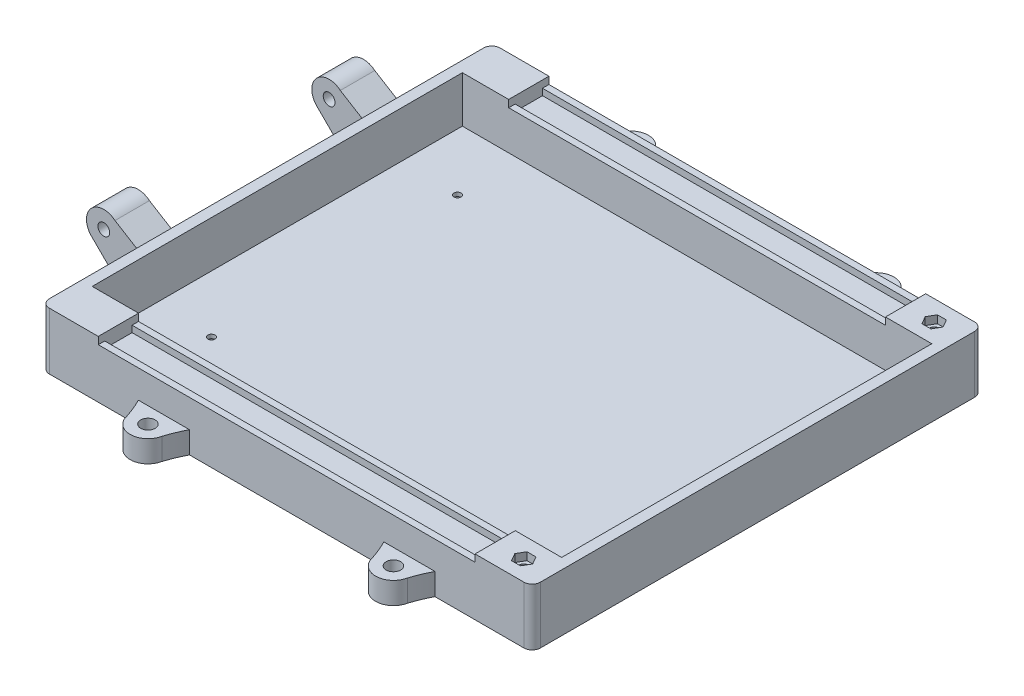
SolidWorks part; units mm, degrees
note: '?' marks a value the reader was unsure of.
ref_plane "Front Plane" through (0, 0, 0) normal (0, 0, 1) x (1, 0, 0)
ref_plane "Top Plane" through (0, 0, 0) normal (0, 1, 0) x (1, 0, 0)
ref_plane "Right Plane" through (0, 0, 0) normal (1, 0, 0) x (0, 0, -1)
sketch "Sketch18" plane through (0, 0, 0) normal (0, 1, 0) x (1, 0, 0)
  line L1 (-114.02, -85.96) -> (114.02, -85.96)
  line L2 (-114.02, -85.96) -> (-114.02, 85.96)
  line L3 (-114.02, 85.96) -> (114.02, 85.96)
  line L4 (114.02, -85.96) -> (114.02, 85.96)
  line L5 (-114.02, -85.96) -> (114.02, 85.96) construction
  line L6 (-114.02, 85.96) -> (114.02, -85.96) construction
  point P0 (0, 0)
  dimension "D1" = 171.92
  dimension "D2" = 228.04
extrude "Boss-Extrude6" add sketch "Sketch18" along normal blind 26.5
sketch "Sketch20" plane through (0, 26.5, 0) normal (0, 1, 0) x (1, 0, 0)
  line L0 (114.02, 85.96) -> (-114.02, 85.96) construction
  line L1 (109.02, -85.96) -> (-109.02, -85.96)
  line L2 (109.02, -85.96) -> (109.02, 85.96)
  line L3 (109.02, 85.96) -> (-109.02, 85.96)
  line L4 (-109.02, -85.96) -> (-109.02, 85.96)
  line L5 (109.02, -85.96) -> (-109.02, 85.96) construction
  line L6 (109.02, 85.96) -> (-109.02, -85.96) construction
  point P0 (0, 0)
  dimension "D1" = 218.04
extrude "Cut-Extrude6" cut sketch "Sketch20" against normal blind 21.5
sketch "Sketch22" plane through (0, 0, 0) normal (0, 1, 0) x (1, 0, 0)
  line L1 (-114.02, -85.96) -> (114.02, -85.96)
  line L2 (-114.02, -85.96) -> (-114.02, -104.66)
  line L3 (-114.02, -104.66) -> (114.02, -104.66)
  line L4 (114.02, -85.96) -> (114.02, -104.66)
  dimension "D1" = 18.7
extrude "Boss-Extrude7" add sketch "Sketch22" along normal blind 26.5
sketch "Sketch23" plane through (0, 0, 0) normal (0, 1, 0) x (1, 0, 0)
  line L1 (114.02, 85.96) -> (-114.02, 85.96)
  line L2 (114.02, 85.96) -> (114.02, 104.66)
  line L3 (114.02, 104.66) -> (-114.02, 104.66)
  line L4 (-114.02, 85.96) -> (-114.02, 104.66)
  dimension "D1" = 18.7
extrude "Boss-Extrude8" add sketch "Sketch23" along normal blind 26.5
sketch "Sketch24" plane through (0, 26.5, 0) normal (0, 1, 0) x (1, 0, 0)
  line L1 (-87.5, 104.66) -> (87.5, 104.66)
  line L2 (-87.5, 104.66) -> (-87.5, 85.96)
  line L3 (-87.5, 85.96) -> (87.5, 85.96)
  line L4 (87.5, 104.66) -> (87.5, 85.96)
  dimension "D1" = 18.7
  dimension "D2" = 175
extrude "Cut-Extrude7" cut sketch "Sketch24" against normal blind 3.35
sketch "Sketch25" plane through (0, 26.5, 0) normal (0, 1, 0) x (1, 0, 0)
  line L1 (-87.5, -85.96) -> (87.5, -85.96)
  line L2 (-87.5, -85.96) -> (-87.5, -104.66)
  line L3 (-87.5, -104.66) -> (87.5, -104.66)
  line L4 (87.5, -85.96) -> (87.5, -104.66)
  dimension "D1" = 175
  dimension "D2" = 18.7
extrude "Cut-Extrude8" cut sketch "Sketch25" against normal blind 3.35
ref_point "Point2"
ref_point "Point3"
sketch "Sketch27" plane through (0, 23.15, 0) normal (0, 1, 0) x (1, 0, 0)
  line L0 (-87.5, -85.96) -> (-87.5, -104.66) construction
  line L1 (87.5, -88.96) -> (-87.5, -88.96)
  line L2 (87.5, -88.96) -> (87.5, -101.66)
  line L3 (87.5, -101.66) -> (-87.5, -101.66)
  line L4 (-87.5, -88.96) -> (-87.5, -101.66)
  line L5 (87.5, -88.96) -> (-87.5, -101.66) construction
  line L6 (87.5, -101.66) -> (-87.5, -88.96) construction
  point P0 (0, -95.31)
  dimension "D1" = 12.7
extrude "Cut-Extrude9" cut sketch "Sketch27" against normal blind 3
sketch "Sketch28" plane through (0, 23.15, 0) normal (0, 1, 0) x (1, 0, 0)
  line L0 (-87.5, 104.66) -> (-87.5, 85.96) construction
  line L1 (87.5, 88.96) -> (-87.5, 88.96)
  line L2 (87.5, 88.96) -> (87.5, 101.66)
  line L3 (87.5, 101.66) -> (-87.5, 101.66)
  line L4 (-87.5, 88.96) -> (-87.5, 101.66)
  line L5 (87.5, 88.96) -> (-87.5, 101.66) construction
  line L6 (87.5, 101.66) -> (-87.5, 88.96) construction
  point P0 (0, 95.31)
  dimension "D1" = 12.7
extrude "Cut-Extrude10" cut sketch "Sketch28" against normal blind 3
sketch "Sketch29" plane through (0, 5, 0) normal (0, 1, 0) x (1, 0, 0)
  line L0 (-109.02, 85.96) -> (-109.02, -85.96) construction
  line L1 (106.02, -60.96) -> (-87.02, -60.96)
  line L2 (106.02, -60.96) -> (106.02, 60.96)
  line L3 (106.02, 60.96) -> (-87.02, 60.96)
  line L4 (-87.02, -60.96) -> (-87.02, 60.96)
  line L5 (106.02, -60.96) -> (-87.02, 60.96) construction
  line L6 (106.02, 60.96) -> (-87.02, -60.96) construction
  line L7 (109.02, 85.96) -> (-109.02, 85.96) construction
  line L8 (-109.02, -85.96) -> (109.02, -85.96) construction
  point P0 (0, 0)
  point P5 (0, 0)
  point P6 (-82.448, 57.15)
  point P7 (0, 0)
  point P9 (101.448, 57.15)
  point P11 (0, 0)
  point P12 (101.448, -57.15)
  point P13 (13.5784, -27.1819)
  point P15 (-82.448, -57.15)
  point P20 (-87.02, 0)
  point P21 (-109.02, 0)
  dimension "D5" = 22
  dimension "D1" = 193.04
  dimension "D2" = 121.92
  dimension "D3" = 3.81
  dimension "D4" = 4.572
  dimension "D6" = 3.81
  dimension "D7" = 4.572
  dimension "D9" = 4.572
  dimension "D10" = 3.81
  dimension "D12" = 3.81
  dimension "D13" = 4.572
sketch "Sketch31" plane through (0, 5, 0) normal (0, 1, 0) x (1, 0, 0)
  circle A0 centre (-82.448, 57.15) radius 1.65
  circle A1 centre (101.448, 57.15) radius 1.651
  circle A2 centre (101.448, -57.15) radius 1.651
  circle A3 centre (-82.448, -57.15) radius 1.65
  dimension "D1" = 3.3
  dimension "D2" = 3.302
  dimension "D3" = 3.302
  dimension "D4" = 3.3
extrude "Cut-Extrude15" cut sketch "Sketch31" against normal blind 1.825
sketch "Sketch33" plane through (0, 0, 0) normal (0, -1, 0) x (1, 0, 0)
  line L0 (-87.02, 60.96) -> (-87.02, -60.96) construction
  line L1 (-79.317, -58.9577) -> (-79.317, -55.3423)
  line L2 (-79.317, -55.3423) -> (-82.448, -53.5346)
  line L3 (-82.448, -53.5346) -> (-85.579, -55.3423)
  line L4 (-85.579, -55.3423) -> (-85.579, -58.9577)
  line L5 (-85.579, -58.9577) -> (-82.448, -60.7654)
  line L6 (-82.448, -60.7654) -> (-79.317, -58.9577)
  line L7 (106.02, 60.96) -> (106.02, -60.96) construction
  line L8 (104.579, -58.9577) -> (104.579, -55.3423)
  line L9 (104.579, -55.3423) -> (101.448, -53.5346)
  line L10 (101.448, -53.5346) -> (98.317, -55.3423)
  line L11 (98.317, -55.3423) -> (98.317, -58.9577)
  line L12 (98.317, -58.9577) -> (101.448, -60.7654)
  line L13 (101.448, -60.7654) -> (104.579, -58.9577)
  line L15 (-79.317, 58.9577) -> (-82.448, 60.7654)
  line L16 (-82.448, 60.7654) -> (-85.579, 58.9577)
  line L17 (-85.579, 58.9577) -> (-85.579, 55.3423)
  line L18 (-85.579, 55.3423) -> (-82.448, 53.5346)
  line L19 (-82.448, 53.5346) -> (-79.317, 55.3423)
  line L20 (-79.317, 55.3423) -> (-79.317, 58.9577)
  line L21 (98.317, 58.9577) -> (98.317, 55.3423)
  line L22 (98.317, 55.3423) -> (101.448, 53.5346)
  line L23 (101.448, 53.5346) -> (104.579, 55.3423)
  line L24 (104.579, 55.3423) -> (104.579, 58.9577)
  line L25 (104.579, 58.9577) -> (101.448, 60.7654)
  line L26 (101.448, 60.7654) -> (98.317, 58.9577)
  circle A0 centre (-82.448, -57.15) radius 3.131 construction
  circle A1 centre (101.448, -57.15) radius 3.131 construction
  circle A2 centre (-82.448, 57.15) radius 3.131 construction
  circle A3 centre (101.448, 57.15) radius 3.131 construction
  dimension "D3" = 3.6154
  dimension "D1" = 3.6154
  dimension "D2" = 3.6154
  dimension "D4" = 3.6154
extrude "Cut-Extrude17" cut sketch "Sketch33" against normal blind 3.175
ref_plane "Plane5" through (0, 0, -52.33) normal (0, 0, 1) x (1, 0, 0)
ref_plane "Plane6" through (0, 0, 0) normal (0, 0, 1) x (1, 0, 0)
sketch "Sketch38" plane through (0, 0, -52.33) normal (0, 0, 1) x (1, 0, 0)
  line L0 (-114.02, 0) -> (-134.4559, 20.3526)
  line L5 (-114.02, 26.5) -> (-114.02, 0)
  line L6 (-114.02, 26.5) -> (-124.0621, 32.6474)
  arc A0 (-124.0621, 32.6474) -> (-134.4559, 20.3526) centre (-129.259, 26.5) ccw
  circle A1 centre (-129.259, 26.5) radius 2.75
  point P4 (-68.3041, 23.6257)
  point P5 (-141.759, 26.5)
  point P6 (0, 0)
  point P7 (-135.4355, 22.8555)
  point P10 (-75.8962, 42.2221)
  point P11 (0, 0)
  point P13 (0, 0)
  point P14 (0, 0)
  point P17 (0, 0)
  point P18 (0, 0)
  dimension "D1" = 11.7743
  dimension "D4" = 5.5
  dimension "D3" = 8.0498
  dimension "D2" = 28.8418
  dimension "D5" = 26.5
  dimension "D6" = 121.474
extrude "Boss-Extrude12" add sketch "Sketch38" along normal blind 8 and the other way blind 8
mirror "Mirror2" about plane through (0, 0, 0) normal (0, 0, 1) of "Boss-Extrude12"
sketch "Sketch39" plane through (0, 26.5, 0) normal (0, 1, 0) x (1, 0, 0)
  line L0 (87.5, 85.96) -> (87.5, 104.66) construction
  line L1 (114.02, 104.66) -> (87.5, 104.66) construction
  circle A0 centre (100.76, 95.31) radius 2.2
  point P5 (87.5, 95.31)
  point P10 (100.76, 104.66)
  dimension "D1" = 4.4
extrude "Cut-Extrude18" cut sketch "Sketch39" against normal blind 26.5
sketch "Sketch40" plane through (0, 0, 0) normal (0, -1, 0) x (1, 0, 0)
  circle A0 centre (100.76, -95.31) radius 4.4
  dimension "D1" = 8.8
extrude "Cut-Extrude19" cut sketch "Sketch40" against normal blind 20.9
mirror "Mirror3" about plane through (0, 0, 0) normal (0, 0, 1) of "Cut-Extrude18"
mirror "Mirror4" about plane through (0, 0, 0) normal (0, 0, 1) of "Cut-Extrude19"
fillet "Fillet1" radius 3.81 4 edges at (114.02, 13.25, 104.66) (-114.02, 13.25, 104.66) (-114.02, 13.25, -104.66) (114.02, 13.25, -104.66)
sketch "Sketch41" plane through (0, 26.5, 0) normal (0, 1, 0) x (1, 0, 0)
  line L1 (98.6815, -91.71) -> (96.6031, -95.31)
  line L2 (96.6031, -95.31) -> (98.6815, -98.91)
  line L3 (98.6815, -98.91) -> (102.8385, -98.91)
  line L4 (102.8385, -98.91) -> (104.9169, -95.31)
  line L5 (104.9169, -95.31) -> (102.8385, -91.71)
  line L6 (102.8385, -91.71) -> (98.6815, -91.71)
  circle A0 centre (100.76, -95.31) radius 3.6 construction
  point P1 (100.76, -98.91)
  point P10 (104.9169, -95.31)
  dimension "D1" = 7.2
extrude "Cut-Extrude20" cut sketch "Sketch41" against normal blind 3.6
mirror "Mirror5" about plane through (0, 0, 0) normal (0, 0, 1) of "Cut-Extrude20"
ref_plane "Plane7" through (-50.76, 0, 0) normal (-1, 0, 0) x (0, 0, 1)
ref_axis "Axis2" through (0, 0, 104.66) along (0, 0, 1)?
ref_plane "Plane8" through (12.5, 0, 0) normal (-1, 0, 0) x (0, 0, 1)
sketch "Sketch47" plane through (0, 0, 0) normal (0, -1, 0) x (1, 0, 0)
  line L0 (51.3982, -115.1797) -> (56.8971, -118.4848) construction
  line L10 (62.509, -115.3752) -> (62.6218, -108.9603) construction
  line L11 (56.8971, -118.4848) -> (62.509, -115.3752) construction
  line L12 (57.1229, -105.6552) -> (51.511, -108.7648) construction
  line L13 (51.511, -108.7648) -> (51.3982, -115.1797) construction
  line L14 (62.6218, -108.9603) -> (57.1229, -105.6552) construction
  line L15 (57.1229, -104.6552) -> (57.1229, -105.6552)
  line L18 (-62.6218, -108.9603) -> (-57.1229, -105.6552) construction
  line L19 (-51.511, -108.7648) -> (-51.3982, -115.1797) construction
  line L20 (-57.1229, -105.6552) -> (-51.511, -108.7648) construction
  line L21 (-56.8971, -118.4848) -> (-62.509, -115.3752) construction
  line L22 (-62.509, -115.3752) -> (-62.6218, -108.9603) construction
  line L23 (-51.3982, -115.1797) -> (-56.8971, -118.4848) construction
  line L24 (-57.1229, -104.6552) -> (-57.1229, -105.6552)
  circle A6 centre (57.01, -112.07) radius 3.3782
  circle A7 centre (57.01, -112.07) radius 6.4158 construction
  arc A8 (48.9032, -113.7572) -> (65.1168, -113.7572) centre (57.01, -112.07) ccw
  arc A9 (68.8852, -104.6552) -> (65.1168, -113.7572) centre (121.2285, -131.657) ccw
  circle A10 centre (57.01, -112.07) radius 5.5562 construction
  arc A11 (45.1348, -104.6552) -> (48.9032, -113.7572) centre (-7.2085, -131.657) cw
  circle A12 centre (-57.01, -112.07) radius 5.5562 construction
  circle A13 centre (-57.01, -112.07) radius 6.4158 construction
  arc A14 (-45.1348, -104.6552) -> (-48.9032, -113.7572) centre (7.2085, -131.657) ccw
  arc A15 (-68.8852, -104.6552) -> (-65.1168, -113.7572) centre (-121.2285, -131.657) cw
  arc A16 (-48.9032, -113.7572) -> (-65.1168, -113.7572) centre (-57.01, -112.07) cw
  circle A17 centre (-57.01, -112.07) radius 3.3782
  dimension "D7" = 6.7564
  dimension "D6" = 11.1125
  dimension "D8" = 1
extrude "Boss-Extrude14" add sketch "Sketch47" against normal blind 10.16
mirror "Mirror6" about plane through (0, 0, 0) normal (0, 0, 1) of "Boss-Extrude14"
